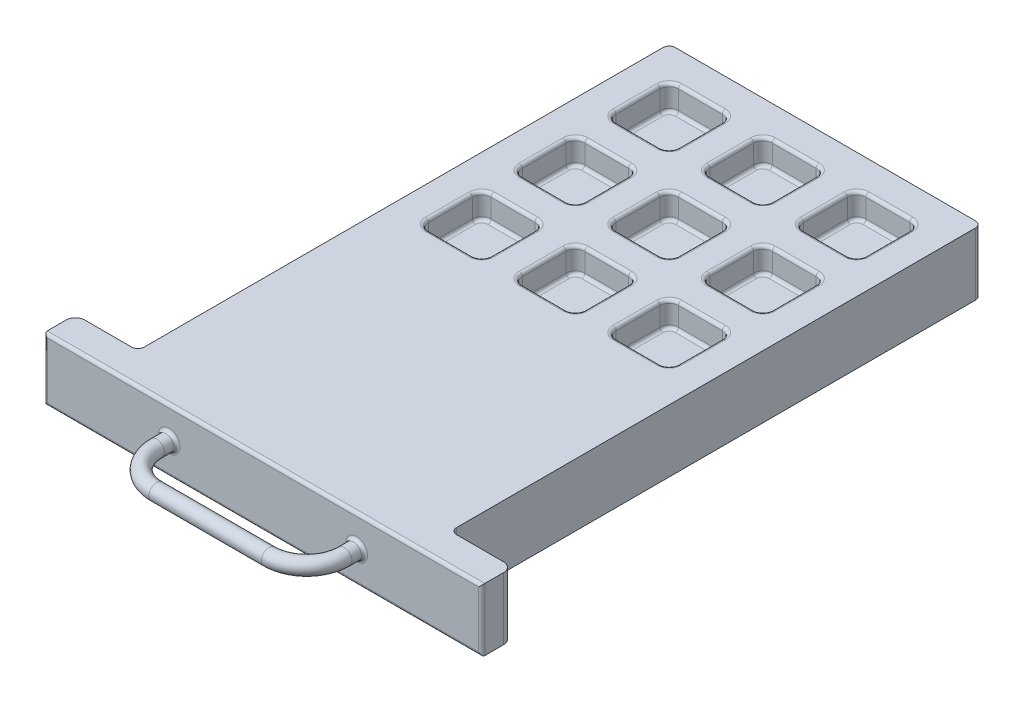
SolidWorks part; units mm, degrees
material "1060 合金"
ref_plane "前视基准面" through (0, 0, 0) normal (0, 0, 1) x (1, 0, 0)
ref_plane "上视基准面" through (0, 0, 0) normal (0, 1, 0) x (1, 0, 0)
ref_plane "右视基准面" through (0, 0, 0) normal (1, 0, 0) x (0, 0, -1)
sketch "草图1" plane through (0, 0, 0) normal (0, 1, 0) x (1, 0, 0)
  line L0 (0, -323.2072) -> (0, 393.6425) construction
  line L1 (-48, 180) -> (48, 180)
  line L2 (50, 178) -> (50, 12)
  line L3 (52, 10) -> (67, 10)
  line L4 (70, 7) -> (70, 0)
  line L5 (70, 0) -> (-70, 0)
  line L6 (-70, 7) -> (-70, 0)
  line L7 (-52, 10) -> (-67, 10)
  line L8 (-50, 178) -> (-50, 12)
  arc A0 (52, 10) -> (50, 12) centre (52, 12) cw
  arc A1 (50, 178) -> (48, 180) centre (48, 178) ccw
  arc A2 (70, 7) -> (67, 10) centre (67, 7) ccw
  arc A3 (-70, 7) -> (-67, 10) centre (-67, 7) cw
  arc A4 (-50, 178) -> (-48, 180) centre (-48, 178) cw
  arc A5 (-52, 10) -> (-50, 12) centre (-52, 12) ccw
  point P3 (-70, 10)
  point P9 (0, 180)
  point P13 (50, 180)
  point P16 (70, 10)
  point P27 (0, 0)
  point P28 (-50, 180)
  dimension "D5" = 2
  dimension "D6" = 3
  dimension "D1" = 170
  dimension "D2" = 70
  dimension "D3" = 50
  dimension "D4" = 10
extrude "凸台-拉伸1" add sketch "草图1" along normal blind 20
sketch "草图3" plane through (0, 20, 0) normal (0, 1, 0) x (1, 0, 0)
  line L0 (0, 180) -> (0, 0) construction
  line L1 (48, 180) -> (-48, 180) construction
  line L3 (-40, 90) -> (40, 90) construction
  line L4 (-40, 90) -> (-40, 170) construction
  line L5 (-40, 170) -> (40, 170) construction
  line L6 (40, 90) -> (40, 170) construction
  line L7 (-40, 90) -> (40, 170) construction
  line L8 (-40, 170) -> (40, 90) construction
  line L9 (67, 10) -> (52, 10) construction
  line L10 (-37, 170) -> (-23, 170)
  line L11 (-40, 167) -> (-40, 153)
  line L12 (-37, 150) -> (-23, 150)
  line L13 (-20, 167) -> (-20, 153)
  arc A0 (-20, 153) -> (-23, 150) centre (-23, 153) cw
  arc A1 (-37, 150) -> (-40, 153) centre (-37, 153) cw
  arc A2 (-20, 167) -> (-23, 170) centre (-23, 167) ccw
  arc A3 (-37, 170) -> (-40, 167) centre (-37, 167) ccw
  point P5 (0, 130)
  point P19 (-40, 150)
  point P22 (-20, 170)
  point P26 (59.5, 10)
  dimension "D6" = 3
  dimension "D1" = 120
  dimension "D2" = 80
  dimension "D3" = 80
  dimension "D4" = 20
  dimension "D5" = 20
extrude "切除-拉伸3" cut sketch "草图3" against normal blind 8
pattern_linear "阵列(线性)3" count 3 spacing 30 along (1, 0, 0) count 3 spacing 30 along (0, 0, 1) of "切除-拉伸3"
ref_plane "基准面1" through (0, 10, 0) normal (0, -1, 0) x (-1, 0, 0)
sketch "草图4" plane through (0, 10, 0) normal (0, -1, 0) x (-1, 0, 0)
  line L0 (0, 0) -> (0, -14.2627) construction
  line L1 (-30, 0) -> (-30, -4)
  line L2 (70, 0) -> (-70, 0) construction
  line L3 (-18, -16) -> (18, -16)
  line L4 (30, 0) -> (30, -4)
  arc A0 (-18, -16) -> (-30, -4) centre (-18, -4) cw
  arc A1 (18, -16) -> (30, -4) centre (18, -4) ccw
  point P8 (30, -16)
  point P10 (-30, -16)
  point P15 (0, -16)
  dimension "D3" = 12
  dimension "D1" = 30
  dimension "D2" = 16
sketch "草图5" plane through (0, 0, 0) normal (0, 0, 1) x (1, 0, 0)
  circle A0 centre (-30, 10) radius 2.5
  dimension "D1" = 5
sweep "扫描1" add profiles "草图5" path "草图4"
fillet "Fillet4" radius 1 6 edges at (27.5, 10, 0) (-27.5, 10, 0) (-70, 10, 0) (0, 20, 0) (70, 10, 0) (0, 0, 0)
fillet "Fillet5" radius 1 16 edges at (-20, 12, -100) (-20, 20, -100) (-30, 12, -110) (-30, 20, -110) (-39.1213, 12, -109.1213) (-39.1213, 20, -109.1213) (-30, 12, -90) (-30, 20, -90) (-39.1213, 12, -90.8787) (-39.1213, 20, -90.8787) (-20.8787, 12, -90.8787) (-20.8787, 20, -90.8787) (-20.8787, 12, -109.1213) (-20.8787, 20, -109.1213) (-40, 12, -100) (-40, 20, -100)
fillet "Fillet6" radius 1 128 edges at (30, 12, -110) (39.1213, 12, -109.1213) (40, 12, -100) (39.1213, 12, -90.8787) (30, 12, -90) (20.8787, 12, -90.8787) (20, 12, -100) (30, 20, -110) (39.1213, 20, -109.1213) (40, 20, -100) (39.1213, 20, -90.8787) (30, 20, -90) (20.8787, 20, -90.8787) (20, 20, -100) (30, 12, -140) (39.1213, 12, -139.1213) (40, 12, -130) (39.1213, 12, -120.8787) (30, 12, -120) (20.8787, 12, -120.8787) (20, 12, -130) (30, 20, -140) (39.1213, 20, -139.1213) (40, 20, -130) (39.1213, 20, -120.8787) (30, 20, -120) (20.8787, 20, -120.8787) (20, 20, -130) (30, 12, -170) (39.1213, 12, -169.1213) (40, 12, -160) (39.1213, 12, -150.8787) (30, 12, -150) (20.8787, 12, -150.8787) (20, 12, -160) (30, 20, -170) (39.1213, 20, -169.1213) (40, 20, -160) (39.1213, 20, -150.8787) (30, 20, -150) (20.8787, 20, -150.8787) (20, 20, -160) (0, 12, -170) (9.1213, 12, -169.1213) (10, 12, -160) (9.1213, 12, -150.8787) (0, 12, -150) (-9.1213, 12, -150.8787) (-10, 12, -160) (0, 20, -170) (9.1213, 20, -169.1213) (10, 20, -160) (9.1213, 20, -150.8787) (0, 20, -150) (-9.1213, 20, -150.8787) (-10, 20, -160) (-30, 12, -170) (-20.8787, 12, -169.1213) (-20, 12, -160) (-20.8787, 12, -150.8787) (-30, 12, -150) (-39.1213, 12, -150.8787) (-40, 12, -160) (-30, 20, -170) (-20.8787, 20, -169.1213) (-20, 20, -160) (-20.8787, 20, -150.8787) (-30, 20, -150) (-39.1213, 20, -150.8787) (-40, 20, -160) (0, 12, -140) (9.1213, 12, -139.1213) (10, 12, -130) (9.1213, 12, -120.8787) (0, 12, -120) (-9.1213, 12, -120.8787) (-10, 12, -130) (0, 20, -140) (9.1213, 20, -139.1213) (10, 20, -130) (9.1213, 20, -120.8787) (0, 20, -120) (-9.1213, 20, -120.8787) (-10, 20, -130) (0, 12, -110) (9.1213, 12, -109.1213) (10, 12, -100) (9.1213, 12, -90.8787) (0, 12, -90) (-9.1213, 12, -90.8787) (-10, 12, -100) (0, 20, -110) (9.1213, 20, -109.1213) (10, 20, -100) (9.1213, 20, -90.8787) (0, 20, -90) (-9.1213, 20, -90.8787) (-10, 20, -100) (-30, 12, -140) (-20.8787, 12, -139.1213) (-20, 12, -130) (-20.8787, 12, -120.8787) (-30, 12, -120) (-39.1213, 12, -120.8787) (-40, 12, -130) (-30, 20, -140) (-20.8787, 20, -139.1213) (-20, 20, -130) (-20.8787, 20, -120.8787) (-30, 20, -120) (-39.1213, 20, -120.8787) (-40, 20, -130) (20.8787, 12, -109.1213) (20.8787, 20, -109.1213) (20.8787, 12, -139.1213) (20.8787, 20, -139.1213) (20.8787, 12, -169.1213) (20.8787, 20, -169.1213) (-9.1213, 12, -169.1213) (-9.1213, 20, -169.1213) (-39.1213, 12, -169.1213) (-39.1213, 20, -169.1213) (-9.1213, 12, -139.1213) (-9.1213, 20, -139.1213) (-9.1213, 12, -109.1213) (-9.1213, 20, -109.1213) (-39.1213, 12, -139.1213) (-39.1213, 20, -139.1213)
